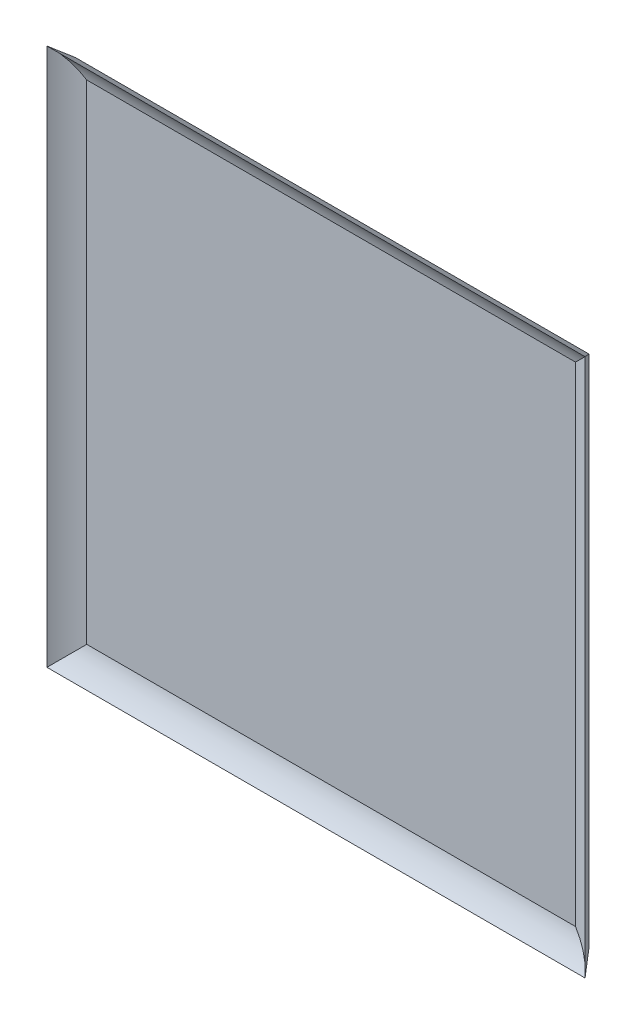
SolidWorks part; units mm, degrees
ref_plane "前视基准面" through (0, 0, 0) normal (0, 0, 1) x (1, 0, 0)
ref_plane "上视基准面" through (0, 0, 0) normal (0, 1, 0) x (1, 0, 0)
ref_plane "右视基准面" through (0, 0, 0) normal (1, 0, 0) x (0, 0, -1)
other "Configuration Table"
sketch "草图1" plane through (0, 0, 0) normal (0, 0, 1) x (1, 0, 0)
  line L11 (-17.5, -167.5) -> (167.5, -167.5)
  line L12 (-17.5, -167.5) -> (-17.5, 17.5)
  line L13 (-17.5, 17.5) -> (167.5, 17.5)
  line L14 (167.5, -167.5) -> (167.5, 17.5)
sketch "草图3" plane through (0, 0, 20) normal (0, 0, 1) x (1, 0, 0)
  line L7 (-32.4602, 32.2748) -> (182.5398, 32.2748)
  line L8 (-32.4602, 32.2748) -> (-32.4602, -182.7252)
  line L9 (-32.4602, -182.7252) -> (182.5398, -182.7252)
  line L10 (182.5398, 32.2748) -> (182.5398, -182.7252)
  point P12 (75.0398, -75.2252)
  dimension "D1" = 215
  dimension "D2" = 215
loft "放样1" add profiles "草图3", "草图1" connector at (-32.4602, 32.2748, 20) connector at (-17.5, 17.5, 0)
shell "抽壳2" thickness 3 removed face at (75.0398, -75.2252, 20)
sketch "草图4" plane through (0, 0, 3) normal (0, 0, 1) x (1, 0, 0)
  line L0 (75, 15.9864) -> (75, -182.7252)
  line L1 (166.0024, 15.9864) -> (-15.9976, 15.9864) construction
  line L2 (-32.4602, -182.7252) -> (182.5398, -182.7252) construction
  line L3 (-32.4602, -75.2252) -> (182.5398, -75.2252)
  line L4 (-32.4602, 32.2748) -> (-32.4602, -182.7252) construction
  line L5 (182.5398, -182.7252) -> (182.5398, 32.2748) construction
  circle A0 centre (66.25, -75.2252) radius 7 construction
  circle A1 centre (66.25, -75.2252) radius 4
  circle A2 centre (66.25, -68.2252) radius 1.5
  circle A3 centre (66.25, -82.2252) radius 1.5
  circle A4 centre (73.25, -75.2252) radius 1.5
  circle A5 centre (59.25, -75.2252) radius 1.5
  circle A6 centre (84.75, -75.2252) radius 1.5
  circle A7 centre (47.75, -75.2252) radius 1.5
  dimension "D1" = 8
  dimension "D2" = 14
  dimension "D3" = 3
  dimension "D4" = 3
  dimension "D5" = 3
  dimension "D6" = 3
  dimension "D7" = 3
  dimension "D8" = 3
  dimension "D9" = 37
  dimension "D10" = 18.5
extrude "切除-拉伸1" cut sketch "草图4" against normal blind 10 contours L3 A6 | L3 A6 | A3 | L3 A4 | L3 A4 | A2 | L3 A5 | L3 A5 | L3 A7 | L3 A7 region at (47.75, -74.5886, 3) region at (84.75, -74.5886, 3) region at (84.75, -75.8619, 3) region at (73.25, -74.5886, 3) region at (73.25, -75.8619, 3) region at (59.25, -74.5886, 3) region at (59.25, -75.8619, 3) region at (47.75, -75.8619, 3) region at (66.25, -68.2252, 3) region at (66.25, -82.2252, 3)
sketch "草图6" plane through (0, 0, 3) normal (0, 0, 1) x (1, 0, 0)
  line L2 (38.15, -62.5) -> (34.15, -62.5)
  line L5 (38.15, -75) -> (38.15, -62.5)
  line L6 (38.15, -75) -> (38.15, -87.5)
  line L7 (94.35, -75) -> (94.35, -62.5)
  line L8 (94.35, -75) -> (94.35, -87.5)
  line L9 (94.35, -62.5) -> (98.35, -62.5)
  line L11 (98.35, -87.5) -> (94.35, -87.5)
  line L12 (98.35, -87.5) -> (101.35, -87.5)
  line L13 (101.35, -87.5) -> (101.35, -84.5)
  line L14 (98.35, -62.5) -> (101.35, -62.5)
  line L15 (101.35, -62.5) -> (101.35, -65.5)
  line L16 (38.15, -87.5) -> (34.15, -87.5)
  line L17 (34.15, -62.5) -> (31.15, -62.5)
  line L18 (31.15, -62.5) -> (31.15, -65.5)
  line L19 (34.15, -87.5) -> (31.15, -87.5)
  line L20 (31.15, -87.5) -> (31.15, -84.5)
  line L21 (31.15, -65.5) -> (34.15, -65.5)
  line L22 (31.15, -84.5) -> (34.15, -84.5)
  line L23 (34.15, -84.5) -> (34.15, -65.5)
  line L24 (101.35, -65.5) -> (98.35, -65.5)
  line L25 (101.35, -84.5) -> (98.35, -84.5)
  line L26 (98.35, -84.5) -> (98.35, -65.5)
extrude "凸台-拉伸1" add sketch "草图6" against normal blind 40.5
sketch "草图7" plane through (98.35, 0, 0) normal (1, 0, 0) x (0, 0, -1)
  line L0 (0, -65.5) -> (0, -84.5)
  line L1 (0, -75) -> (16.5, -75)
  line L2 (16.5, -75) -> (33.5, -75)
  line L3 (33.5, -75) -> (37.5, -75)
  line L4 (37.5, -84.5) -> (37.5, -65.5) construction
  circle A0 centre (16.5, -75) radius 1.51
  circle A1 centre (33.5, -75) radius 1.51
extrude "切除-拉伸2" cut sketch "草图7" against normal blind 100 contours L2 A0 L1 | L1 A0 L2 | L3 A1 L2 | L2 A1 L3 region at (98.35, -74.3591, -16.5) region at (98.35, -74.3591, -33.5) region at (98.35, -75.6409, -33.5) region at (98.35, -75.6409, -16.5)
sketch "草图8" plane through (0, 0, 3) normal (0, 0, 1) x (1, 0, 0)
  circle A0 centre (66.25, -68.2252) radius 1.5
  circle A1 centre (59.25, -75.2252) radius 1.5
  circle A2 centre (47.75, -75.2252) radius 1.5
  circle A3 centre (73.25, -75.2252) radius 1.5
  circle A4 centre (84.75, -75.2252) radius 1.5
  circle A5 centre (66.25, -82.2252) radius 1.5
  circle M2 centre (84.75, -75.2252) radius 1.5
  circle M3 centre (59.25, -75.2252) radius 1.5
  circle M5 centre (73.25, -75.2252) radius 1.5
  circle M6 centre (66.25, -82.2252) radius 1.5
  circle M7 centre (47.75, -75.2252) radius 1.5
extrude "凸台-拉伸2" add sketch "草图8" against normal blind 3 contours M6 | M5 | M2 | M3 | M7 | A0 region at (59.25, -75.2252, 3) region at (47.75, -75.2252, 3) region at (73.25, -75.2252, 3) region at (84.75, -75.2252, 3) region at (66.25, -82.2252, 3)
sketch "草图9" plane through (0, 0, 0) normal (0, 0, -1) x (-1, 0, 0)
  line L3 (-73.5858, -76.4142) -> (0, -2.8284)
  line L4 (17.5, 17.5) -> (17.5, -167.5) construction
  line L5 (0, -2.8284) -> (0, 0)
  line L6 (-72.7486, -69.9202) -> (-2.8284, 0)
  line L7 (-167.5, 17.5) -> (17.5, 17.5) construction
  line L8 (-2.8284, 0) -> (0, 0)
  line L9 (-72.7486, -69.9202) -> (-150, -147.1716)
  line L10 (-167.5, -167.5) -> (-167.5, 17.5) construction
  line L11 (-150, -147.1716) -> (-150, -150)
  line L12 (-73.5858, -76.4142) -> (-147.1716, -150)
  line L14 (17.5, -167.5) -> (-167.5, -167.5) construction
  line L15 (-147.1716, -150) -> (-150, -150)
extrude "凸台-拉伸3" add sketch "草图9" along normal blind 4 contours L9 L11 L15 L12 L3 L5 L8 L6
sketch "草图10" plane through (0, 0, 0) normal (0, 0, -1) x (-1, 0, 0)
  line L3 (-106.6693, -40.5023) -> (-147.1716, 17.5)
  line L4 (-167.5, 17.5) -> (17.5, 17.5) construction
  line L5 (-147.1716, 17.5) -> (-167.5, 17.5)
  line L6 (-121.9738, -30.8546) -> (-167.5, 34.3423)
  line L7 (-167.5, -167.5) -> (-167.5, 17.5) construction
  line L8 (-167.5, 34.3423) -> (-167.5, 17.5)
  line L9 (-106.6693, -40.5023) -> (17.5, -218.322)
  line L10 (17.5, 17.5) -> (17.5, -167.5) construction
  line L11 (17.5, -218.322) -> (17.5, -167.5)
  line L12 (-121.9738, -30.8546) -> (-26.556, -167.5)
  line L13 (17.5, -167.5) -> (-167.5, -167.5) construction
  line L14 (-26.556, -167.5) -> (17.5, -167.5)
extrude "凸台-拉伸4" add sketch "草图10" along normal blind 4 contours L3 L5 L8 L6 L12 L14 L11 L9 rebuild error yes
sketch "草图11" plane through (0, 0, -4) normal (0, 0, -1) x (-1, 0, 0)
  line L1 (-94.35, -62.5) -> (-38.15, -62.5)
  line L2 (-94.35, -62.5) -> (-94.35, -87.5)
  line L3 (-94.35, -87.5) -> (-38.15, -87.5)
  line L4 (-38.15, -62.5) -> (-38.15, -87.5)
extrude "切除-拉伸3" cut sketch "草图11" against normal blind 4 contours L2 L1 L4 L3
sketch "草图12" plane through (0, 0, 20) normal (0, 0, 1) x (1, 0, 0)
  line L1 (182.5398, 32.2748) -> (185.5398, 32.2748)
  line L2 (182.5398, 32.2748) -> (182.5398, -182.7252)
  line L3 (182.5398, -182.7252) -> (185.5398, -182.7252)
  line L4 (185.5398, 32.2748) -> (185.5398, -182.7252)
extrude "凸台-拉伸5" add sketch "草图12" against normal blind 10 separate body
sketch "草图13" plane through (185.5398, 0, 0) normal (1, 0, 0) x (0, 0, -1)
  line L0 (-10, -182.7252) -> (-10, 32.2748) construction
  line L1 (-20, 32.2748) -> (-10, 32.2748)
  line L2 (-20, 32.2748) -> (-20, -182.7252)
  line L3 (-20, -182.7252) -> (-10, -182.7252)
  line L4 (-10, 32.2748) -> (-10, -182.7252)
extrude "切除-拉伸4" cut sketch "草图13" against normal blind 300
sketch "草图15" plane through (0, 0, -4) normal (0, 0, -1) x (-1, 0, 0)
  line L1 (-154.8521, -152.6743) -> (-38.15, -152.6743)
  line L2 (-154.8521, -152.6743) -> (-154.8521, -87.5)
  line L3 (-154.8521, -87.5) -> (-38.15, -87.5)
  line L4 (-38.15, -152.6743) -> (-38.15, -87.5)
  line L5 (-94.35, -62.5) -> (17.5, -62.5)
  line L6 (-94.35, -62.5) -> (-94.35, 17.5)
  line L7 (-94.35, 17.5) -> (17.5, 17.5)
  line L8 (17.5, -62.5) -> (17.5, 17.5)
extrude "切除-拉伸5" cut sketch "草图15" against normal blind 4 contours L6 L5 L8 L7 | L2 L1 L4 L3
sketch "草图16" plane through (0, 0, 0) normal (0, 0, -1) x (-1, 0, 0)
  line L3 (-123.7693, -120.9409) -> (-167.5, -164.6716)
  line L4 (-134.8709, -12.3007) -> (-164.6716, 17.5)
  line L5 (-167.5, 17.5) -> (17.5, 17.5) construction
  line L6 (-164.6716, 17.5) -> (-167.5, 17.5)
  line L7 (-140.0326, -12.7959) -> (-167.5, 14.6716)
  line L8 (-167.5, -167.5) -> (-167.5, 17.5) construction
  line L9 (-167.5, 14.6716) -> (-167.5, 17.5)
  line L10 (-140.0326, -12.7959) -> (14.6716, -167.5)
  line L11 (17.5, -167.5) -> (-167.5, -167.5) construction
  line L12 (14.6716, -167.5) -> (17.5, -167.5)
  line L14 (-134.8709, -12.3007) -> (17.5, -164.6716)
  line L15 (17.5, 17.5) -> (17.5, -167.5) construction
  line L16 (17.5, -164.6716) -> (17.5, -167.5)
  line L17 (-167.5, -164.6716) -> (-167.5, -167.5)
  line L18 (-116.3532, -119.1816) -> (-164.6716, -167.5)
  line L19 (-164.6716, -167.5) -> (-167.5, -167.5)
  line L20 (-116.3532, -119.1816) -> (17.5, 14.6716)
  line L21 (17.5, 14.6716) -> (17.5, 17.5)
  line L22 (-123.7693, -120.9409) -> (14.6716, 17.5)
  line L23 (14.6716, 17.5) -> (17.5, 17.5)
extrude "凸台-拉伸6" add sketch "草图16" along normal blind 4 contours L10 L22 L14 L4 L7 | L20 L10 L14 | L3 L17 L19 L18 L20 L21 L23 L22 region at (121.6045, -28.3955, 0) region at (28.3955, -121.6045, 0)
sketch "草图17" plane through (0, 0, 0) normal (0, 0, -1) x (-1, 0, 0)
  line L1 (-94.35, -62.5) -> (-38.15, -62.5)
  line L2 (-94.35, -62.5) -> (-94.35, -87.5)
  line L3 (-94.35, -87.5) -> (-38.15, -87.5)
  line L4 (-38.15, -62.5) -> (-38.15, -87.5)
extrude "切除-拉伸6" cut sketch "草图17" along normal blind 4 contours L2 L1 L4 L3
sketch "草图18" plane through (0, 0, 0) normal (0, 0, -1) x (-1, 0, 0)
  line L3 (-75, -119.25) -> (-33.5784, -119.25)
  line L7 (-65.3284, -87.5) -> (14.6716, -167.5) construction
  line L8 (-33.5784, -119.25) -> (-31.5784, -121.25)
  line L9 (-65.3284, -87.5) -> (14.6716, -167.5) construction
  line L10 (-75, -123.25) -> (-29.5784, -123.25)
  line L11 (-29.5784, -123.25) -> (-31.5784, -121.25)
  line L12 (-75, -119.25) -> (-116.4216, -119.25)
  line L13 (-164.6716, -167.5) -> (-84.6716, -87.5) construction
  line L14 (-75, -123.25) -> (-120.4216, -123.25)
  line L15 (-120.4216, -123.25) -> (-116.4216, -119.25)
  line L18 (-119.25, -75) -> (-119.25, -116.4216)
  line L19 (-90.3284, -87.5) -> (-167.5, -164.6716) construction
  line L20 (-119.25, -116.4216) -> (-121.25, -118.4216)
  line L21 (-123.25, -75) -> (-123.25, -120.4216)
  line L22 (-123.25, -120.4216) -> (-121.25, -118.4216)
  line L23 (-119.25, -75) -> (-119.25, -33.5784)
  line L24 (-167.5, 14.6716) -> (-90.3284, -62.5) construction
  line L25 (-123.25, -75) -> (-123.25, -29.5784)
  line L26 (-167.5, 14.6716) -> (-90.3284, -62.5) construction
  line L27 (-123.25, -29.5784) -> (-119.25, -33.5784)
  line L30 (-75, -30.75) -> (-116.4216, -30.75)
  line L31 (-164.6716, 17.5) -> (-84.6716, -62.5) construction
  line L32 (-75, -26.75) -> (-120.4216, -26.75)
  line L33 (-164.6716, 17.5) -> (-84.6716, -62.5) construction
  line L34 (-120.4216, -26.75) -> (-116.4216, -30.75)
  line L35 (-75, -30.75) -> (-33.5784, -30.75)
  line L36 (14.6716, 17.5) -> (-65.3284, -62.5) construction
  line L37 (-75, -26.75) -> (-29.5784, -26.75)
  line L38 (-65.3284, -62.5) -> (14.6716, 17.5) construction
  line L39 (-29.5784, -26.75) -> (-33.5784, -30.75)
  line L40 (-30.75, -33.5784) -> (-26.75, -29.5784)
  line L42 (-26.75, -75) -> (-26.75, -29.5784)
  line L43 (-59.6716, -62.5) -> (17.5, 14.6716) construction
  line L44 (-30.75, -75) -> (-30.75, -33.5784)
  line L45 (-30.75, -75) -> (-30.75, -116.4216)
  line L46 (-59.6716, -87.5) -> (17.5, -164.6716) construction
  line L47 (-26.75, -75) -> (-26.75, -120.4216)
  line L48 (-30.75, -116.4216) -> (-26.75, -120.4216)
extrude "凸台-拉伸7" add sketch "草图18" along normal blind 4
sketch "草图20" plane through (0, 0, 0) normal (0, 0, -1) x (-1, 0, 0)
  line L0 (-94.35, -62.5) -> (-94.35, -87.5)
  line L1 (-94.35, -87.5) -> (-38.15, -87.5)
  line L2 (-38.15, -87.5) -> (-38.15, -62.5)
  line L3 (-38.15, -62.5) -> (-94.35, -62.5)
  line L4 (-66.25, -75) -> (-66.25, -82)
  line L5 (-66.25, -75) -> (-47.75, -75)
  line L6 (-66.25, -75) -> (-84.75, -75)
  line L7 (-66.25, -75) -> (-66.25, -68)
  circle A0 centre (-84.75, -75) radius 1.5
  circle A1 centre (-47.75, -75) radius 1.5
  circle A2 centre (-66.25, -68) radius 1.5
  circle A3 centre (-66.25, -82) radius 1.5
extrude "切除-拉伸7" cut sketch "草图20" against normal blind 10 contours A2 | A0 | A3 | A1 region at (65.2193, -80.9693, 0) region at (47.75, -73.5424, 0) region at (86.2076, -75, 0) region at (67.2807, -66.9693, 0)
sketch "草图21" plane through (0, 0, -37.5) normal (0, 0, -1) x (-1, 0, 0)
  line L1 (-167.5, 17.5) -> (17.5, 17.5)
  line L2 (-167.5, 17.5) -> (-167.5, -167.5)
  line L3 (-167.5, -167.5) -> (17.5, -167.5)
  line L4 (17.5, 17.5) -> (17.5, -167.5)
extrude "切除-拉伸8" cut sketch "草图21" against normal blind 37.5
sketch "草图22" plane through (0, 0, 0) normal (0, 0, -1) x (-1, 0, 0)
  line L1 (17.5, 17.5) -> (-167.5, 17.5)
  line L2 (17.5, 17.5) -> (17.5, -167.5)
  line L3 (17.5, -167.5) -> (-167.5, -167.5)
  line L4 (-167.5, 17.5) -> (-167.5, -167.5)
  circle A0 centre (-66.25, -68) radius 1.5
  circle A1 centre (-66.25, -82) radius 1.5
  circle A2 centre (-84.75, -75) radius 1.5
  circle A3 centre (-47.75, -75) radius 1.5
extrude "凸台-拉伸8" add sketch "草图22" along normal blind 1 contours L2 L1 L4 L3 | A3 | A0 | A2 | A1
sketch "草图24" plane through (0, 0, 3) normal (0, 0, 1) x (1, 0, 0)
  circle A0 centre (66.25, -68) radius 3
  circle A1 centre (66.25, -82) radius 3
  circle A2 centre (47.75, -75) radius 3
  circle A3 centre (84.75, -75) radius 3
  circle M4 centre (66.25, -68) radius 1.5
  circle M5 centre (84.75, -75) radius 1.5
  circle M6 centre (66.25, -82) radius 1.5
extrude "切除-拉伸9" cut sketch "草图24" against normal blind 2 contours A0 M4 | A1 M6 | A3 M5 | A2 region at (63.3349, -68, 3) region at (63.3349, -82, 3) region at (81.8349, -75, 3)
sketch "草图25" plane through (0, 0, -1) normal (0, 0, -1) x (-1, 0, 0)
  line L0 (-167.5, 17.5) -> (17.5, -167.5)
  line L1 (-75, -75) -> (-75, -68)
  line L2 (-75, -75) -> (-75, -82)
  line L4 (-75, -75) -> (-56.5, -75)
  line L5 (-75, -75) -> (-93.5, -75)
  circle A0 centre (-75, -68) radius 1.51
  circle A1 centre (-75, -82) radius 1.51
  circle A2 centre (-93.5, -75) radius 1.51
  circle A3 centre (-56.5, -75) radius 1.51
extrude "切除-拉伸10" cut sketch "草图25" against normal blind 10 contours A2 | A0 | A1 | A3 region at (76.0375, -66.9625, -1) region at (73.9625, -80.9625, -1) region at (56.5, -73.5327, -1) region at (94.9673, -75, -1)
sketch "草图26" plane through (0, 0, -1) normal (0, 0, -1) x (-1, 0, 0)
  circle A0 centre (-84.75, -75) radius 1.5
  circle A1 centre (-66.25, -68) radius 1.5
  circle A2 centre (-66.25, -82) radius 1.5
  circle A3 centre (-47.75, -75) radius 1.5
extrude "凸台-拉伸9" add sketch "草图26" against normal blind 4 contours A0 | A1 | A2 | A3
sketch "草图28" plane through (0, 0, 3) normal (0, 0, 1) x (1, 0, 0)
  circle A0 centre (84.75, -75) radius 3
  circle A1 centre (66.25, -68) radius 3
  circle A2 centre (47.75, -75) radius 3
  circle A3 centre (66.25, -82) radius 3
extrude "凸台-拉伸10" add sketch "草图28" against normal blind 4
sketch "草图29" plane through (0, 0, 3) normal (0, 0, 1) x (1, 0, 0)
  circle A0 centre (75, -68) radius 3
  circle A1 centre (75, -82) radius 3
  circle A2 centre (93.5, -75) radius 3
  circle A3 centre (56.5, -75) radius 3
extrude "切除-拉伸11" cut sketch "草图29" against normal blind 2
sketch "草图30" plane through (-11.2214, 0, -8.3937) normal (-0.8008, 0, -0.599) x (-0.599, 0, 0.8008)
  line L0 (22.9702, 23.2126) -> (21.9702, 23.2126)
  line L1 (22.9702, -175.1126) -> (22.9702, 24.8874) construction
  line L3 (21.9702, 23.2126) -> (22.9702, 23.2126)
  line L4 (21.9702, 23.2126) -> (21.9702, 25.5215)
  line L5 (21.9702, 25.5215) -> (22.9702, 25.5215)
  line L6 (22.9702, 23.2126) -> (22.9702, 25.5215)
  line L7 (21.9702, 23.2126) -> (24.4729, 23.2126)
  line L8 (21.9702, 23.2126) -> (21.9702, -177.3761)
  line L9 (21.9702, -177.3761) -> (24.4729, -177.3761)
  line L10 (24.4729, 23.2126) -> (24.4729, -177.3761)
  line M2 (10.4822, -167.5) -> (22.9702, -175.1126)
  line M3 (22.9702, -175.1126) -> (22.9702, 24.8874)
  line M4 (22.9702, 24.8874) -> (10.4822, 17.5)
extrude "切除-拉伸12" cut sketch "草图30" against normal blind 10 contours L6 L5 L4 M4 | L4 L0 M3 M4 | L0 L8 M2 M3 | L10 L7 L8 L9 M3 M2 region at (-24.6808, -75.7977, 9.5998) region at (-24.702, 23.9127, 9.6282) region at (-25.4237, -77.9182, 10.593) region at (-24.6489, 25.0409, 9.5572)
sketch "草图31" plane through (0, 11.3215, -8.3636) normal (0, 0.8043, -0.5942) x (1, 0, 0)
  line L0 (-9.3628, -22.831) -> (-9.3628, -21.831)
  line L1 (-23.3106, -22.831) -> (175.0199, -22.831) construction
  line L3 (-9.3628, -21.831) -> (-28.9973, -21.831)
  line L4 (-9.3628, -21.831) -> (-9.3628, -26.3658)
  line L5 (-9.3628, -26.3658) -> (-28.9973, -26.3658)
  line L6 (-28.9973, -21.831) -> (-28.9973, -26.3658)
  line L7 (-9.3628, -21.831) -> (184.8283, -21.831)
  line L8 (-9.3628, -21.831) -> (-9.3628, -29.9137)
  line L9 (-9.3628, -29.9137) -> (184.8283, -29.9137)
  line L10 (184.8283, -21.831) -> (184.8283, -29.9137)
  line M2 (-24.3811, -21.8355) -> (-23.3106, -22.831)
  line M3 (-23.3106, -22.831) -> (175.0199, -22.831)
  line M4 (175.0199, -22.831) -> (167.5, -10.3983)
  line M8 (-17.5, -10.3983) -> (-24.3811, -21.8355)
extrude "切除-拉伸13" cut sketch "草图31" against normal blind 10 contours L3 L6 L5 L4 M3 M2 M8 | L10 L7 L4 L8 L9 M4 M3 | L0 L3 M8 M2 M3 | L7 L0 M3 M4 region at (-16.6088, 24.5866, 9.5929) region at (88.4044, 26.974, 12.8246) region at (-19.6796, 25.8452, 11.2966) region at (82.6774, 24.5904, 9.5981)
sketch "草图32" plane through (106.9956, 0, -80.4593) normal (0.7992, 0, -0.601) x (-0.601, 0, -0.7992)
  line L0 (-113.1822, -69.7237) -> (-112.1822, -69.7237)
  line L1 (-113.1822, 23.2044) -> (-113.1822, -175.1126) construction
  line L3 (-112.1822, -69.7237) -> (-120.0099, -69.7237)
  line L4 (-112.1822, -69.7237) -> (-112.1822, 28.1473)
  line L5 (-112.1822, 28.1473) -> (-120.0099, 28.1473)
  line L6 (-120.0099, -69.7237) -> (-120.0099, 28.1473)
  line L7 (-112.1822, -69.7237) -> (-120.0099, -69.7237)
  line L8 (-112.1822, -69.7237) -> (-112.1822, -178.2761)
  line L9 (-112.1822, -178.2761) -> (-120.0099, -178.2761)
  line L10 (-120.0099, -69.7237) -> (-120.0099, -178.2761)
  line M3 (-112.1758, 24.2932) -> (-113.1822, 23.2044)
  line M4 (-113.1822, 23.2044) -> (-113.1822, -175.1126)
  line M5 (-113.1822, -175.1126) -> (-100.6702, -167.5)
extrude "切除-拉伸14" cut sketch "草图32" against normal blind 10 contours L6 L3 L4 L5 M4 M3 | L0 L4 M3 M4 | L3 L10 L9 L8 M5 M4 | L8 L0 M4 M5 region at (174.7188, -22.9887, 9.5996) region at (177.0607, -124.2446, 12.7139) region at (177.0563, -20.4824, 12.7081) region at (174.7197, -122.2662, 9.6008)
sketch "草图33" plane through (0, -106.0449, -80.7279) normal (0, -0.7957, -0.6057) x (1, 0, 0)
  line L0 (69.3935, 114.0259) -> (69.3935, 113.0259)
  line L1 (173.356, 114.0259) -> (-23.3106, 114.0259) construction
  line L3 (69.3935, 113.0259) -> (179.7251, 113.0259)
  line L4 (69.3935, 113.0259) -> (69.3935, 118.677)
  line L5 (69.3935, 118.677) -> (179.7251, 118.677)
  line L6 (179.7251, 113.0259) -> (179.7251, 118.677)
  line L7 (69.3935, 113.0259) -> (-31.9687, 113.0259)
  line L8 (69.3935, 113.0259) -> (69.3935, 127.9963)
  line L9 (69.3935, 127.9963) -> (-31.9687, 127.9963)
  line L10 (-31.9687, 113.0259) -> (-31.9687, 127.9963)
  line M7 (174.4189, 113.0215) -> (173.356, 114.0259)
  line M8 (173.356, 114.0259) -> (-23.3106, 114.0259)
  line M9 (-23.3106, 114.0259) -> (-24.3811, 113.0196)
extrude "切除-拉伸15" cut sketch "草图33" against normal blind 10 contours L3 L6 L5 L4 M8 M7 | L10 L7 L4 L8 L9 M9 M8 | L7 L0 M8 M9 | L0 L3 M7 M8 region at (121.6397, -174.8093, 9.6015) region at (18.4464, -179.3179, 15.524) region at (125.1471, -176.5021, 11.8252) region at (22.775, -174.8092, 9.6014)
sketch "草图36" plane through (-17.5, 0, 0) normal (-1, 0, 0) x (0, 0, 1)
  line L0 (10, 23.2044) -> (9.19, 23.2044)
  line L3 (9.19, 23.2044) -> (10.0434, 23.2044)
  line L4 (9.19, 23.2044) -> (9.19, 24.4576)
  line L5 (9.19, 24.4576) -> (10.0434, 24.4576)
  line L6 (10.0434, 23.2044) -> (10.0434, 24.4576)
  line L7 (9.19, 23.2044) -> (10.8591, 23.2044)
  line L8 (9.19, 23.2044) -> (9.19, -174.8077)
  line L9 (9.19, -174.8077) -> (10.8591, -174.8077)
  line L10 (10.8591, 23.2044) -> (10.8591, -174.8077)
extrude "切除-拉伸19" cut sketch "草图36" against normal blind 200 contours L10 L7 L3 L0 L8 L9 | L3 L6 L5 L4 L0 region at (-17.5, -75.8016, 10.0245) region at (-17.5, 23.831, 9.6167)
sketch "草图37" plane through (-17.5, 0, 0) normal (1, 0, 0) x (0, 0, -1)
  line L0 (-10, -173.4617) -> (-9.19, -173.4617)
  line L1 (-9.19, -170.7256) -> (-9.19, -174.496) construction
  line L3 (-9.19, -173.4617) -> (-10.1205, -173.4617)
  line L4 (-9.19, -173.4617) -> (-9.19, 24.4224)
  line L5 (-9.19, 24.4224) -> (-10.1205, 24.4224)
  line L6 (-10.1205, -173.4617) -> (-10.1205, 24.4224)
  line L7 (-10.1205, -173.4617) -> (-9.19, -173.4617)
  line L8 (-10.1205, -173.4617) -> (-10.1205, -174.6376)
  line L9 (-10.1205, -174.6376) -> (-9.19, -174.6376)
  line L10 (-9.19, -173.4617) -> (-9.19, -174.6376)
  line M1 (-9.19, -170.7256) -> (-10, -171.3423)
  line M2 (-10, -171.3423) -> (-10, -173.4617)
  line M3 (-10, -173.4617) -> (-9.2043, -174.5069)
  line M4 (-9.2043, -174.5069) -> (-9.19, -174.496)
  line M5 (-9.19, -174.496) -> (-9.19, -170.7256)
extrude "切除-拉伸20" cut sketch "草图37" against normal blind 200 contours L10 L3 L8 L9 M4 M3 | L0 M3 M4 M5 | L0 M2 M5 M1 | L6 L3 L4 L5 M2 M1 region at (-17.5, -172.2413, 9.5779) region at (-17.5, -174.2013, 9.7819) region at (-17.5, -73.4647, 9.6561) region at (-17.5, -173.816, 9.4601)
sketch "草图38" plane through (0, 0, -1) normal (0, 0, -1) x (-1, 0, 0)
  line L1 (-167.5, 17.5) -> (17.5, 17.5)
  line L2 (-167.5, 17.5) -> (-167.5, -167.5)
  line L3 (-167.5, -167.5) -> (17.5, -167.5)
  line L4 (17.5, 17.5) -> (17.5, -167.5)
extrude "凸台-拉伸11" add sketch "草图38" against normal blind 4.4
fillet "圆角2" radius 16 4 edges at (-16.2968, -75.018, 3.4) (75.0032, 16.2819, 3.4) (166.3032, -75.018, 3.4) (75.0032, -166.3179, 3.4)
sketch "草图49" plane through (0, -167.5, 0) normal (0, -1, 0) x (1, 0, 0)
  line L0 (-24.3742, 9.19) -> (-20.6278, 9.19)
  line L1 (-20.6278, 9.19) -> (-16.2968, 3.4)
  line L2 (-16.2968, 3.4) -> (166.3032, 3.4) construction
  line L3 (-16.2968, 3.4) -> (166.3032, 3.4) construction
  line L4 (-16.2968, 3.4) -> (166.3032, 3.4)
  line L5 (174.4108, 9.19) -> (170.6572, 9.19)
  line L6 (170.6572, 9.19) -> (166.3032, 3.4)
  line L7 (174.4108, 9.19) -> (167.5, 0)
  line L8 (167.5, 0) -> (167.5, -1)
  line L9 (167.5, -1) -> (-17.5, -1)
  line L10 (-17.5, -1) -> (-17.5, 0)
  line L11 (-17.5, 0) -> (-24.3742, 9.19)
extrude "切除-拉伸21" cut sketch "草图49" against normal blind 400
sketch "草图50" plane through (0, -167.5, 0) normal (0, 1, 0) x (1, 0, 0)
  line L0 (-24.3742, -9.19) -> (-20.6278, -9.19)
  line L1 (-20.6278, -9.19) -> (-16.2968, -3.4)
  line L2 (-16.2968, -3.4) -> (166.3032, -3.4)
  line L3 (166.3032, -3.4) -> (170.6572, -9.19)
  line L4 (170.6572, -9.19) -> (174.4108, -9.19)
  line L5 (174.4108, -9.19) -> (167.5, 0)
  line L6 (167.5, 0) -> (-17.5, 0)
  line L7 (-17.5, 0) -> (-24.3742, -9.19)
extrude "切除-拉伸22" cut sketch "草图50" against normal blind 400
sketch "草图51" plane through (0, 0, 3.4) normal (0, 0, -1) x (-1, 0, 0)
  line L1 (16.2968, 20.0117) -> (13.2224, 20.0117)
  line L2 (16.2968, 20.0117) -> (16.2968, 14.3122)
  line L3 (16.2968, 14.3122) -> (13.2224, 14.3122)
  line L4 (13.2224, 20.0117) -> (13.2224, 14.3122)
extrude "凸台-拉伸12" add sketch "草图51" along normal blind 2 contours L2 L1 L4 L3
sketch "草图54" plane through (-16.2968, 0, 0) normal (-1, 0, 0) x (0, 0, 1)
  line L0 (9.19, 24.289) -> (3.4, 20.0117)
  line L1 (9.19, 24.289) -> (9.19, 20.5592)
  line L2 (9.19, 20.5592) -> (3.4, 16.2819)
  line L3 (3.4, 20.0117) -> (3.4, 14.3122) construction
  line L5 (3.4, 20.0117) -> (1.4, 20.0117)
  line L6 (1.4, 20.0117) -> (1.4, 14.3122)
  line L7 (1.4, 14.3122) -> (3.4, 14.3122)
  line L8 (3.4, 14.3122) -> (3.4, 16.2819)
  line L9 (9.19, -174.496) -> (9.19, -170.7256)
  line L10 (9.19, -170.7256) -> (3.4, -166.3179)
  line L11 (3.4, -174.496) -> (3.4, -166.3179) construction
  line L12 (3.4, -166.3179) -> (3.4, -170.0883)
  line L13 (3.4, -170.0883) -> (9.19, -174.496)
extrude "切除-拉伸23" cut sketch "草图54" against normal blind 400 contours L2 L8 L7 L6 L5 L0 L1 | L13 L9 L10 L12
sketch "草图55" plane through (-16.2968, 0, 0) normal (1, 0, 0) x (0, 0, -1)
  line L0 (-9.19, 24.289) -> (-3.4, 20.0117)
  line L1 (-3.4, 20.0117) -> (-3.4, 16.2819)
  line L2 (-3.4, 16.2819) -> (-9.19, 20.5592)
  line L3 (-9.19, 20.5592) -> (-9.19, 24.289)
  line L4 (-3.4, -166.3179) -> (-3.4, -170.0883)
  line L5 (-3.4, -170.0883) -> (-9.19, -174.496)
  line L6 (-9.19, -174.496) -> (-9.19, -170.7256)
  line L7 (-9.19, -170.7256) -> (-3.4, -166.3179)
extrude "切除-拉伸24" cut sketch "草图55" against normal blind 400
sketch "草图56" plane through (0, 0, 3.4) normal (0, 0, -1) x (-1, 0, 0)
  line L1 (-166.3032, -166.3179) -> (16.2968, -166.3179)
  line L2 (-166.3032, -166.3179) -> (-166.3032, 16.2819)
  line L3 (-166.3032, 16.2819) -> (16.2968, 16.2819)
  line L4 (16.2968, -166.3179) -> (16.2968, 16.2819)
extrude "凸台-拉伸13" add sketch "草图56" against normal blind 0.4
